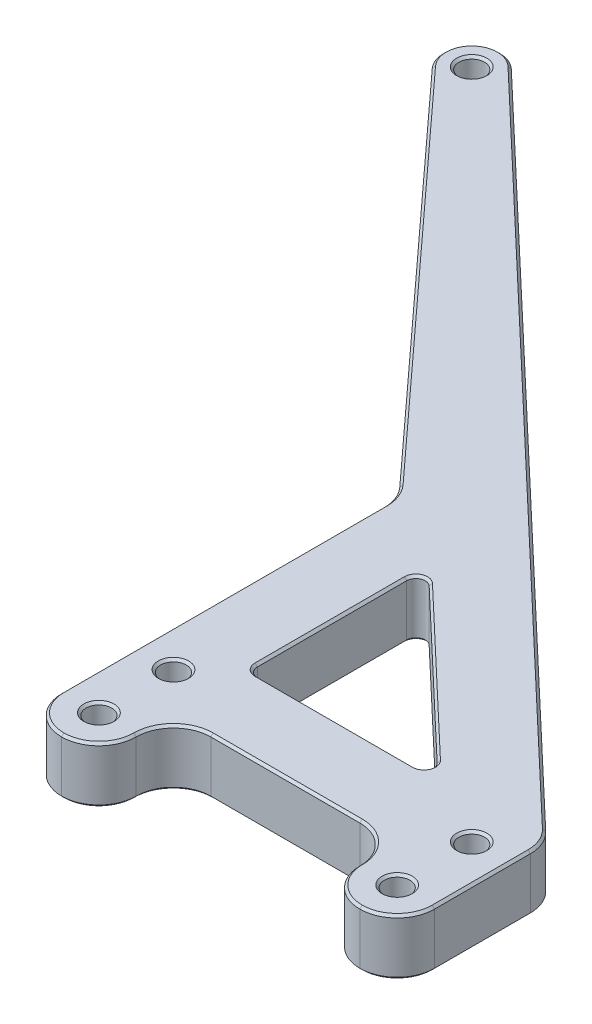
SolidWorks part; units mm, degrees
ref_plane "Front Plane" through (0, 0, 0) normal (0, 0, 1) x (1, 0, 0)
ref_plane "Top Plane" through (0, 0, 0) normal (0, 1, 0) x (1, 0, 0)
ref_plane "Right Plane" through (0, 0, 0) normal (1, 0, 0) x (0, 0, -1)
sketch "Sketch1" plane through (0, 0, 0) normal (0, 1, 0) x (1, 0, 0)
  line L6 (50.8, -6.35) -> (50.7997, -6.35)
  line L7 (-6.35, 0) -> (-6.35, 54.969)
  line L8 (-8.0135, 59.2538) -> (-67.0149, 123.7864)
  line L9 (-60.2214, 130.4543) -> (55.1715, 20.9279)
  line L10 (57.15, 16.3222) -> (57.15, 0)
  line L11 (44.45, -0.0003) -> (44.45, 0.0003)
  line L12 (38.1003, 6.35) -> (12.6997, 6.35)
  line L13 (6.35, 0.0003) -> (6.35, -0.0003)
  line L14 (0.0003, -6.35) -> (0, -6.35)
  line L15 (35.8166, 21.7889) -> (9.0304, 47.2133)
  line L16 (6.35, 46.0619) -> (6.35, 20.6375)
  line L17 (7.9375, 19.05) -> (34.7237, 19.05)
  circle A0 centre (0, 0) radius 2.1828
  circle A3 centre (50.8, 12.7) radius 2.1828
  circle A4 centre (-63.5, 127) radius 2.1828
  arc A11 (-60.2214, 130.4543) -> (-67.0149, 123.7864) centre (-63.5, 127) ccw
  arc A12 (50.8, -6.35) -> (57.15, 0) centre (50.8, 0) ccw
  arc A13 (0, -6.35) -> (-6.35, 0) centre (0, 0) cw
  arc A14 (55.1715, 20.9279) -> (57.15, 16.3222) centre (50.8, 16.3222) cw
  arc A15 (-6.35, 54.969) -> (-8.0135, 59.2538) centre (-12.7, 54.969) ccw
  circle A16 centre (0, 12.7) radius 2.1828
  circle A17 centre (50.8, 0) radius 2.1828
  arc A18 (12.6997, 6.35) -> (6.35, 0.0003) centre (12.6997, 0.0003) ccw
  arc A19 (44.45, 0.0003) -> (38.1003, 6.35) centre (38.1003, 0.0003) ccw
  arc A20 (6.35, -0.0003) -> (0.0003, -6.35) centre (0.0003, -0.0003) cw
  arc A21 (44.45, -0.0003) -> (50.7997, -6.35) centre (50.7997, -0.0003) ccw
  arc A22 (35.8166, 21.7889) -> (34.7237, 19.05) centre (34.7237, 20.6375) cw
  arc A23 (6.35, 20.6375) -> (7.9375, 19.05) centre (7.9375, 20.6375) ccw
  arc A24 (9.0304, 47.2133) -> (6.35, 46.0619) centre (7.9375, 46.0619) ccw
  point P16 (57.15, -6.35)
  point P19 (-6.35, -6.35)
  point P22 (57.15, 19.05)
  point P25 (-6.35, 57.4343)
  point P37 (44.45, 6.35)
  point P40 (6.35, -6.35)
  point P43 (44.45, -6.35)
  dimension "D5" = 4.3656
  dimension "D6" = 9.525
  dimension "D7" = 6.35
  dimension "D8" = 4.3656
  dimension "D11" = 4.3656
  dimension "D12" = 15.875
  dimension "D20" = 12.7
  dimension "D21" = 6.3497
  dimension "D15" = 6.35
  dimension "D16" = 4.3656
  dimension "D17" = 4.3656
  dimension "D25" = 1.5875
  dimension "D2" = 6.35
  dimension "D3" = 50.8
  dimension "D4" = 12.7
  dimension "D9" = 127
  dimension "D10" = 63.5
  dimension "D13" = 25.4
  dimension "D14" = 63.5
  dimension "D18" = 12.7
  dimension "D19" = 12.7
  dimension "D22" = 12.7
  dimension "D23" = 12.7
  dimension "D24" = 12.7
extrude "Boss-Extrude1" add sketch "Sketch1" along normal blind 9.525
chamfer "Chamfer1" distance 0.3969 angle 45 58 edges at (7.3109, 9.525, -47.5205) (6.35, 9.525, -33.3497) (6.815, 9.525, -19.515) (21.3306, 9.525, -19.05) (36.1982, 9.525, -20.0492) (22.4235, 9.525, -34.5011) (50.8, 9.525, 2.1828) (-63.5, 9.525, -124.8172) (0, 9.525, 2.1828) (50.7999, 9.525, 6.35) (46.3098, 9.525, 4.4902) (44.45, 9.525, 0) (42.5902, 9.525, -4.4902) (25.4, 9.525, -6.35) (8.2098, 9.525, -4.4902) (6.35, 9.525, 0) (4.4902, 9.525, 4.4902) (0.0001, 9.525, 6.35) (-4.4901, 9.525, 4.4901) (-6.35, 9.525, -27.4845) (-6.7805, 9.525, -57.2672) (-37.5142, 9.525, -91.5201) (-66.836, 9.525, -130.3989) (-2.5249, 9.525, -75.6911) (56.6345, 9.525, -18.8285) (57.15, 9.525, -8.1611) (55.2901, 9.525, 4.4901) (50.8, 9.525, -10.5172) (0, 9.525, -10.5172) (21.3306, 0, -19.05) (6.815, 0, -19.515) (6.35, 0, -33.3497) (7.3109, 0, -47.5205) (22.4235, 0, -34.5011) (36.1982, 0, -20.0492) (57.15, 0, -8.1611) (56.6345, 0, -18.8285) (-2.5249, 0, -75.6911) (-66.836, 0, -130.3989) (-37.5142, 0, -91.5201) (-6.7805, 0, -57.2672) (-6.35, 0, -27.4845) (-4.4901, 0, 4.4901) (0.0001, 0, 6.35) (4.4902, 0, 4.4902) (6.35, 0, 0) (8.2098, 0, -4.4902) (25.4, 0, -6.35) (42.5902, 0, -4.4902) (44.45, 0, 0) (46.3098, 0, 4.4902) (50.7999, 0, 6.35) (55.2901, 0, 4.4901) (-63.5, 0, -124.8172) (0, 0, 2.1828) (50.8, 0, -10.5172) (0, 0, -10.5172) (50.8, 0, 2.1828)
